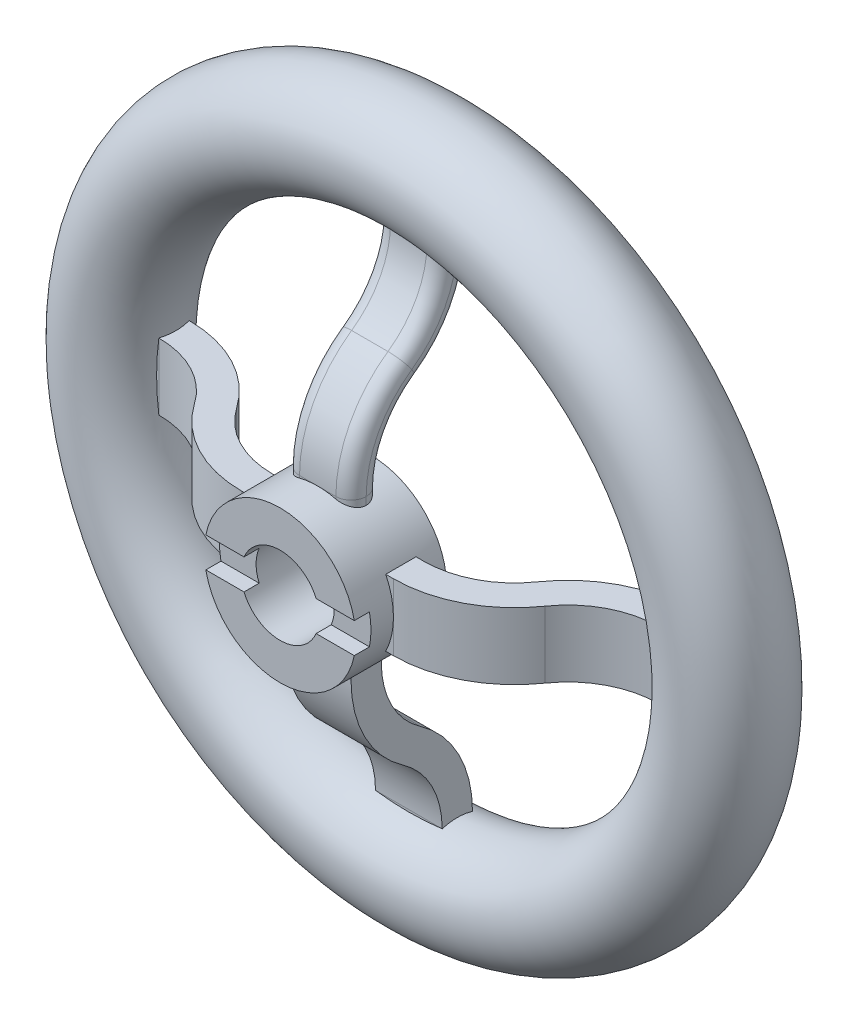
SolidWorks part; units mm, degrees
ref_plane "Alzado" through (0, 0, 0) normal (0, 0, 1) x (1, 0, 0)
ref_plane "Planta" through (0, 0, 0) normal (0, 1, 0) x (1, 0, 0)
ref_plane "Vista lateral" through (0, 0, 0) normal (1, 0, 0) x (0, 0, -1)
sketch "Croquis1" plane through (0, 0, 0) normal (0, 0, 1) x (1, 0, 0)
  circle A0 centre (0, 0) radius 25
  circle A1 centre (0, 0) radius 12.9
  dimension "D1" = 50
  dimension "D2" = 25.8
extrude "Saliente-Extruir1" add sketch "Croquis1" along normal blind 30
sketch "Croquis2" plane through (0, 0, 30) normal (0, 0, 1) x (1, 0, 0)
  line L1 (-29.3708, 5) -> (29.3708, 5)
  line L2 (-29.3708, 5) -> (-29.3708, -5)
  line L3 (-29.3708, -5) -> (29.3708, -5)
  line L4 (29.3708, 5) -> (29.3708, -5)
  line L5 (-29.3708, 5) -> (29.3708, -5) construction
  line L6 (-29.3708, -5) -> (29.3708, 5) construction
  point P0 (0, 0)
  dimension "D1" = 10
extrude "Cortar-Extruir1" cut sketch "Croquis2" against normal blind 5
sketch "Croquis3" plane through (0, 0, 0) normal (1, 0, 0) x (0, 0, -1)
  line L0 (-30, 25) -> (-30, 5) construction
  line L1 (17.5, 100) -> (17.5, 82.5) construction
  line L2 (17.5, 100) -> (35, 100) construction
  line L3 (0, 25) -> (22.4218, 25) construction
  line L4 (17.5, 82.5) -> (-17.5, 82.5) construction
  line L5 (12.5, 82.5) -> (22.5, 82.5)
  line L6 (-7.5782, 25) -> (-17.5782, 25)
  line L7 (12.5, 82.5) -> (12.5, 87.5)
  line L8 (12.5, 87.5) -> (22.5, 87.5)
  line L9 (22.5, 87.5) -> (22.5, 82.5)
  line L10 (-17.5782, 25) -> (-17.5782, 21.5)
  line L11 (-17.5782, 21.5) -> (-7.5782, 21.5)
  line L12 (-7.5782, 21.5) -> (-7.5782, 25)
  circle A0 centre (17.5, 100) radius 17.5 construction
  arc A1 (-0.3907, 57.8571) -> (12.4911, 83.2322) centre (-17.5, 82.5) ccw
  arc A2 (5.3125, 49.6429) -> (22.5, 82.5) centre (-17.5, 82.5) ccw
  arc A3 (5.3125, 49.6429) -> (-7.5782, 25) centre (22.4218, 25) ccw
  arc A4 (-0.3907, 57.8571) -> (-17.5782, 25) centre (22.4218, 25) ccw
  point P20 (17.5, 82.5)
  dimension "D1" = 35
  dimension "D5" = 30
  dimension "D6" = 30
  dimension "D2" = 47.5
  dimension "D3" = 100
  dimension "D4" = 10
  dimension "D7" = 5
  dimension "D8" = 3.5
extrude "Saliente-Extruir2" add sketch "Croquis3" along normal mid plane 22 contours A1 A4 L6 A3 A2 L5 | L9 L8 L7 L5 | L11 L12 L6 L10 region at (0, 85, -17.5) region at (0, 53.75, -2.4609) region at (0, 23.25, 12.5782)
fillet "Redondeo1" radius 5 16 edges at (-11, 85, -12.5) (-11, 68.5946, -9.0827) (-11, 23.725, 17.5782) (-11, 85, -22.5) (-11, 63.9595, -17.9436) (-11, 23.725, 7.5782) (11, 85, -22.5) (11, 63.9595, -17.9436) (11, 23.725, 7.5782) (11, 85, -12.5) (11, 68.5946, -9.0827) (11, 23.725, 17.5782) (-11, 43.5405, 13.0218) (-11, 38.9054, 4.1609) (11, 38.9054, 4.1609) (11, 43.5405, 13.0218)
pattern_circular "MatrizC1" count 4 over 360 about axis through (0, 0, 0) along (0, 0, 1) of "Saliente-Extruir2"
sketch "Croquis5" plane through (0, 0, 0) normal (1, 0, 0) x (0, 0, -1)
  line L0 (0, 0) -> (61.7507, 0) construction
  circle A0 centre (17.5, 100) radius 17.5
revolve "Revolución1" add sketch "Croquis5" angle 360 about L0
